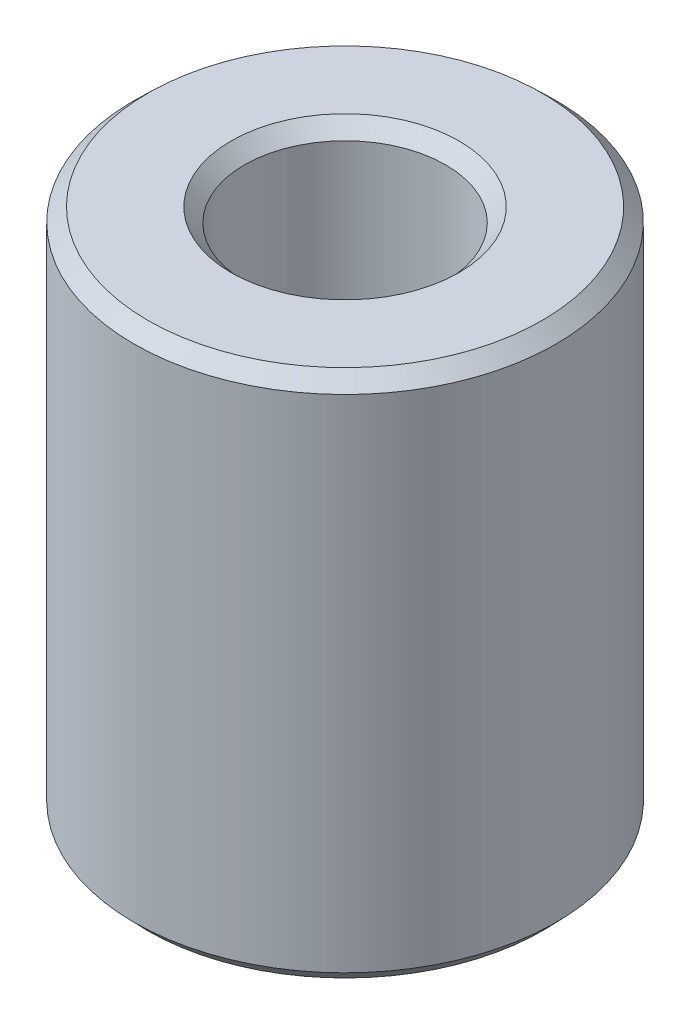
SolidWorks part; units mm, degrees
ref_plane "Front Plane" through (0, 0, 0) normal (0, 0, 1) x (1, 0, 0)
ref_plane "Top Plane" through (0, 0, 0) normal (0, 1, 0) x (1, 0, 0)
ref_plane "Right Plane" through (0, 0, 0) normal (1, 0, 0) x (0, 0, -1)
sketch "Sketch1" plane through (0, 0, 0) normal (0, 1, 0) x (1, 0, 0)
  circle A0 centre (0, 0) radius 57.5
  dimension "SLEEVE_OD" = 115
extrude "Boss-Extrude1" add sketch "Sketch1" along normal blind 143.9735
sketch "Sketch2" plane through (0, 0, 0) normal (0, 1, 0) x (1, 0, 0)
  circle A0 centre (0, 0) radius 27.4172
  dimension "BORE_D" = 54.8345
extrude "Cut-Extrude1" cut sketch "Sketch2" along normal through all
chamfer "Chamfer1" distance 3.6595 angle 46.113 4 edges at (0, 143.9735, 27.4172) (0, 0, 27.4172) (0, 0, 57.5) (0, 143.9735, 57.5) first distance on face at (0, 143.9735, 27.4172) first distance on face at (0, 0, 27.4172) first distance on face at (0, 143.9735, 57.5)
